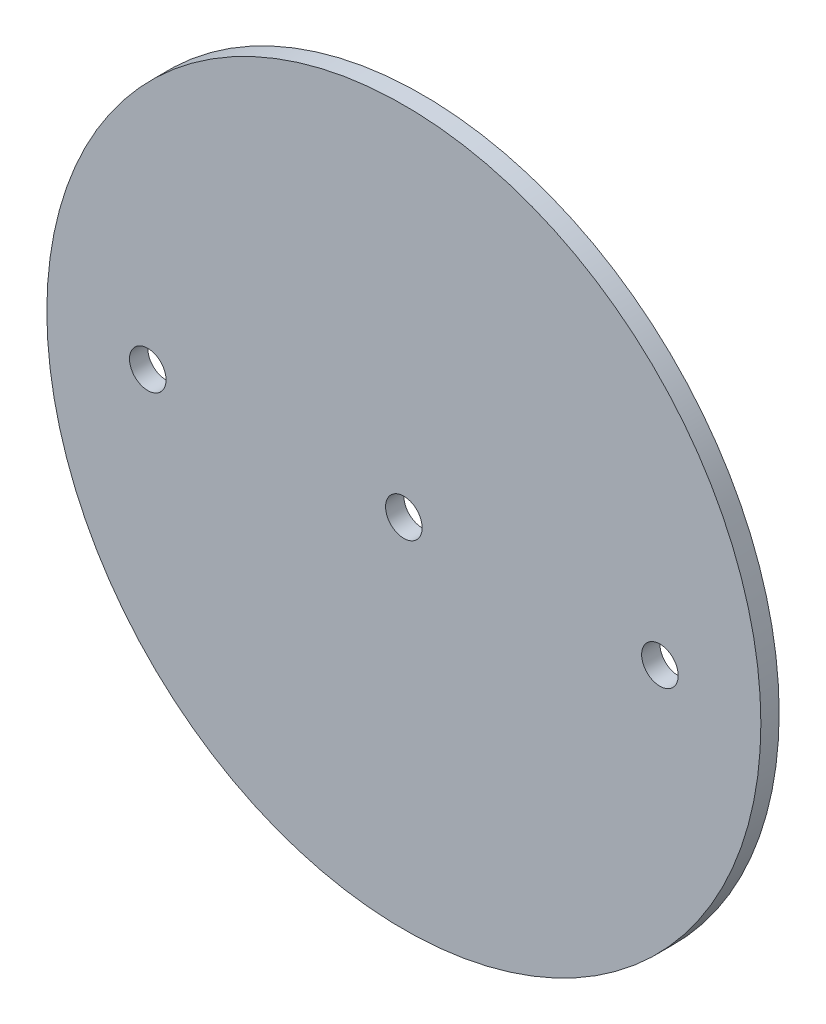
SolidWorks part; units mm, degrees
ref_plane "Front Plane" through (0, 0, 0) normal (0, 0, 1) x (1, 0, 0)
ref_plane "Top Plane" through (0, 0, 0) normal (0, 1, 0) x (1, 0, 0)
ref_plane "Right Plane" through (0, 0, 0) normal (1, 0, 0) x (0, 0, -1)
sketch "Sketch1" plane through (0, 0, 0) normal (0, 0, 1) x (1, 0, 0)
  circle A0 centre (0, 0) radius 61.976
  dimension "D1" = 123.952
extrude "Boss-Extrude1" add sketch "Sketch1" along normal mid plane 3.175
sketch "Sketch2" plane through (0, 0, 1.5875) normal (0, 0, 1) x (1, 0, 0)
  line L0 (-1000, 0) -> (49000, 0) construction
  point P1 (0, 0)
  point P4 (44.45, 0)
  point P5 (-44.45, 0)
  dimension "D1" = 44.45
  dimension "D2" = 88.9
hole_wizard "1/4 (0.25) Diameter Hole1" positions "Sketch2" profile "Sketch3" hole size "1/4" standard "ANSI Inch" end condition through all
sketch "Sketch3" plane through (-44.45, 0, 1.5875) normal (1, 0, 0) x (0, -1, 0)
  line L0 (0, 0) -> (0, 3.175)
  line L1 (0, 3.175) -> (3.175, 3.175)
  line L2 (3.175, 3.175) -> (3.175, 0)
  line L5 (3.175, 0) -> (0, 0)
  line L11 (0, -6.35) -> (0, 107.95) construction
  dimension "Thru Hole Dia." = 6.35
  dimension "Thru Hole Depth" = 3.175
equation "\"AIRFRAME_OD\"= 5.15in"
equation "\"AIRFRAME_ID\"= 5.00in"
equation "\"FLAT_T\"= 0.125in"
equation "\"NOSE_EXP_L\"= 27in"
equation "\"NOSE_SHOULDER_L\"= 5in"
equation "\"MAIN_L\"= 30in"
equation "\"RECO_COUP_L\"= 10in"
equation "\"RECO_SWITCH_L\"= 2in"
equation "\"DROGUE_L\"= 20in"
equation "\"ATS_FORE_COUP_L\"= 5.5in"
equation "\"ATS_AFT_COUP_L\"= 4.5in"
equation "\"LOWER_L\"= 30in"
equation "\"FIN_N\"= 4"
equation "\"CR_AFT_X\"= 0.5in"
equation "\"CR_FORE_X\"= 9.25in"
equation "\"FIN_ROOT\"= 8in"
equation "\"FIN_X\"= 0.75in"
equation "\"MOTOR_OD\"= 3.091in"
equation "\"MOTOR_ID\"= 3.00in"
equation "\"COUPLER_OD\"= 4.998in"
equation "\"COUPLER_ID\"= 4.88in"
equation "\"D1@Sketch1\"=\"COUPLER_ID\""
equation "\"D1@Boss-Extrude1\"=\"FLAT_T\""
equation "\"RECO_ROD_X\"= 3.5in"
equation "\"ATS_ROD_X\"= 3.75in"
equation "\"D1@Sketch2\"=\"RECO_ROD_X\"*0.5"
equation "\"D2@Sketch2\"=\"RECO_ROD_X\""
equation "\"MOTOR_L\"= 14in"
equation "\"MOTOR_LOWER_X\"= 2in"
